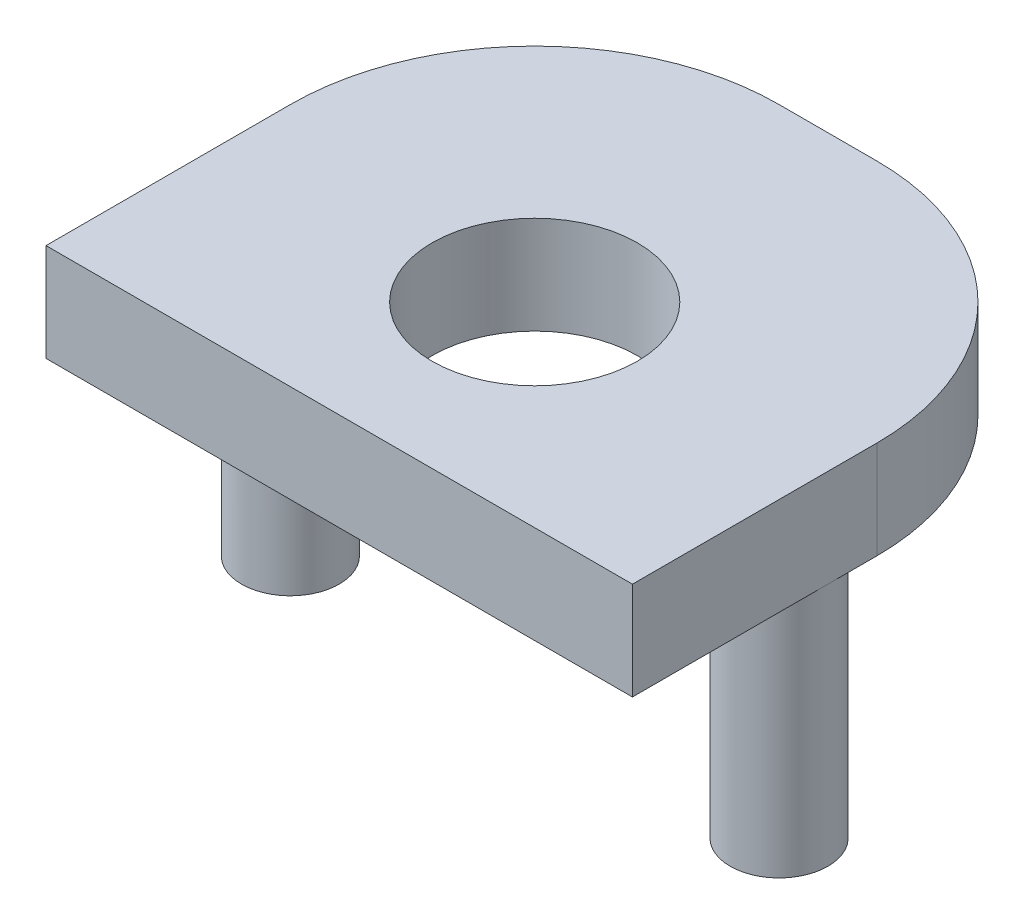
SolidWorks part; units mm, degrees
ref_plane "前视基准面" through (0, 0, 0) normal (0, 0, 1) x (1, 0, 0)
ref_plane "上视基准面" through (0, 0, 0) normal (0, 1, 0) x (1, 0, 0)
ref_plane "右视基准面" through (0, 0, 0) normal (1, 0, 0) x (0, 0, -1)
other "Configuration Table"
sketch "草图1" plane through (0, 0, 0) normal (0, 1, 0) x (1, 0, 0)
  line L0 (0, 0) -> (82.2418, 0) construction
  line L1 (0, 0) -> (0, 65.7222) construction
  circle A0 centre (0, 0) radius 2.1
  circle A1 centre (5, 0) radius 1
  circle A3 centre (-5, 0) radius 1
  circle A4 centre (0, 5) radius 1
  circle A5 centre (0, -5) radius 1 [skipped]
  dimension "D1" = 4.2
  dimension "D2" = 2
  dimension "D3" = 5
  dimension "D4" = 4
extrude "凸台-拉伸1" add sketch "草图1" along normal blind 5 contours A3 | A4 | A1 | A3 | A4 | A1 region at (5, 0, 0) region at (-5, 0, 0) region at (0, 0, -5)
sketch "草图2" plane through (0, 5, 0) normal (0, 1, 0) x (1, 0, 0)
  line L1 (-6, -4) -> (6, -4)
  line L2 (-6, -4) -> (-6, 6)
  line L3 (-6, 6) -> (6, 6)
  line L4 (6, -4) -> (6, 6)
  circle A0 centre (-5, 0) radius 1 construction
  circle A1 centre (0, 5) radius 1 construction
  circle A2 centre (5, 0) radius 1 construction
  dimension "D1" = 4
extrude "凸台-拉伸6" add sketch "草图2" along normal blind 2
extrude "切除-拉伸2" cut sketch "草图1<6>" along normal up to surface (7 mm away) contours A0 region at (0, 0, 0) up to face at (0, 7, -1)
sketch "草图1<6>" plane through (0, 0, 0) normal (0, 1, 0) x (1, 0, 0) same geometry as "草图1"
fillet "圆角1" radius 5 2 edges at (6, 6, -6) (-6, 6, -6)
